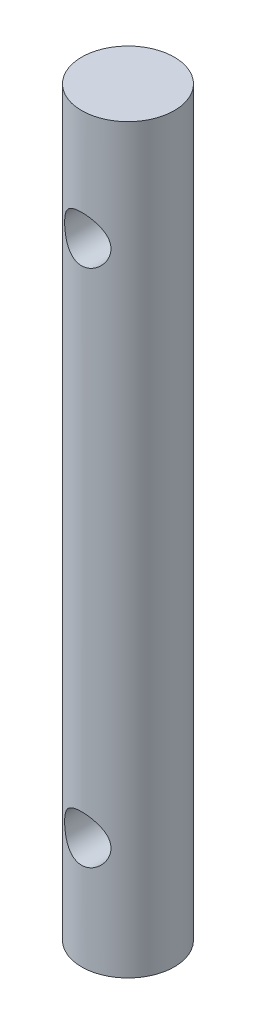
SolidWorks part; units mm, degrees
ref_plane "Front Plane" through (0, 0, 0) normal (0, 0, 1) x (1, 0, 0)
ref_plane "Top Plane" through (0, 0, 0) normal (0, 1, 0) x (1, 0, 0)
ref_plane "Right Plane" through (0, 0, 0) normal (1, 0, 0) x (0, 0, -1)
sketch "Sketch1" plane through (0, 0, 0) normal (0, 1, 0) x (1, 0, 0)
  circle A0 centre (0, 0) radius 3.175
  dimension "D1" = 6.35
extrude "Boss-Extrude1" add sketch "Sketch1" along normal blind 50.8
sketch "Sketch2" plane through (0, 0, 0) normal (0, 0, 1) x (1, 0, 0)
  line L0 (-3.175, 0) -> (3.175, 0) construction
  circle A0 centre (0, 43.18) radius 1.5875
  dimension "D1" = 43.18
  dimension "D2" = 3.175
extrude "Cut-Extrude1" cut sketch "Sketch2" against normal blind 11.176 and the other way blind 12.192
sketch "Sketch3" plane through (0, 0, 0) normal (0, 0, 1) x (1, 0, 0)
  circle A0 centre (0, 7.62) radius 1.5875
  dimension "D1" = 3.175
  dimension "D2" = 7.62
extrude "Cut-Extrude2" cut sketch "Sketch3" against normal blind 11.176 and the other way blind 11.176
